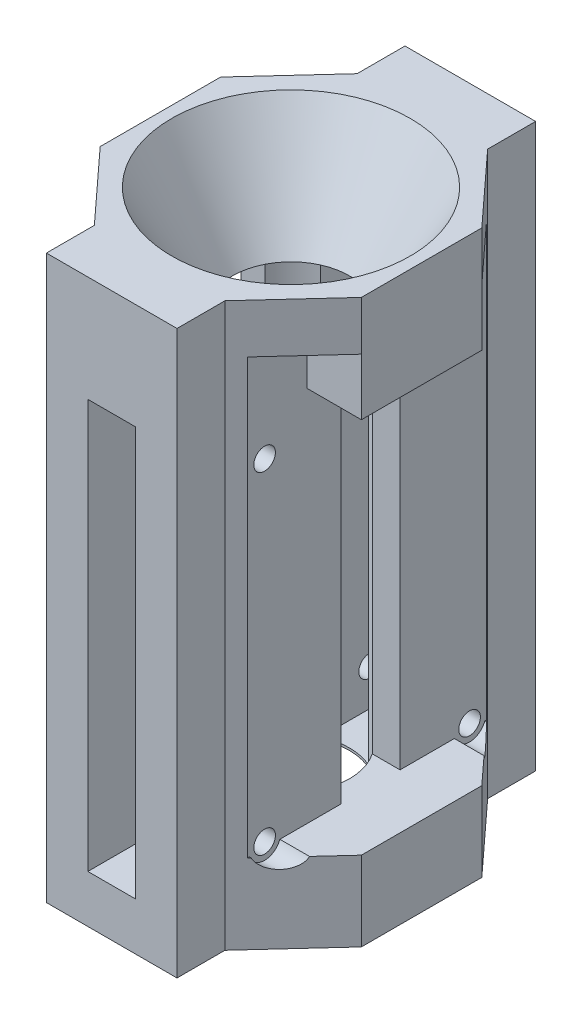
SolidWorks part; units mm, degrees
ref_plane "Alzado" through (0, 0, 0) normal (0, 0, 1) x (1, 0, 0)
ref_plane "Planta" through (0, 0, 0) normal (0, 1, 0) x (1, 0, 0)
ref_plane "Vista lateral" through (0, 0, 0) normal (1, 0, 0) x (0, 0, -1)
sketch "Croquis1" plane through (0, 0, 0) normal (0, 0, 1) x (1, 0, 0)
  line L0 (-110, 93.3) -> (-105, 93.3)
  line L1 (-105, 93.3) -> (-51.5, 0)
  line L2 (-51.5, 0) -> (-51.5, -362)
  line L3 (-51.5, -362) -> (-105, -402)
  line L4 (-105, -402) -> (-110, -402)
  line L5 (-110, -402) -> (-110, 93.3)
  line L6 (0, 0) -> (0, 215.3144) construction
  dimension "D1" = 5
  dimension "D2" = 495.3
  dimension "D3" = 51.5
  dimension "D4" = 362
  dimension "D5" = 110
  dimension "D6" = 40
revolve "Revolución1" add sketch "Croquis1" angle 360 about L6
sketch "Croquis3" plane through (0, 0, 0) normal (1, 0, 0) x (0, 0, -1)
  line L0 (0, 0) -> (0, -402) construction
  line L1 (-110, -402) -> (110, -402) construction
  line L2 (75, 0) -> (75, -362)
  line L3 (-157.87, 0) -> (-75, 0)
  line L4 (-157.87, 0) -> (-157.87, -362)
  line L5 (-157.87, -362) -> (-75, -362)
  line L6 (-75, 0) -> (-75, -362)
  line L7 (157.87, -362) -> (75, -362)
  line L8 (157.87, 0) -> (157.87, -362)
  line L9 (157.87, 0) -> (75, 0)
  dimension "D1" = 362
  dimension "D2" = 47.87
  dimension "D3" = 75
  dimension "D4" = 82.87
  dimension "D5" = 82.87
extrude "Saliente-Extruir1" add sketch "Croquis3" along normal blind 77.5 and the other way blind 77.5
ref_plane "Plano1" through (0, 93.3, 0) normal (0, 1, 0) x (1, 0, 0)
sketch "Croquis4" plane through (0, 93.3, 0) normal (0, 1, 0) x (1, 0, 0)
  line L0 (-77.5, -157.87) -> (77.5, -157.87) construction
  line L1 (-115, 157.87) -> (115, 157.87)
  line L2 (-115, 157.87) -> (-115, -157.87)
  line L3 (-115, -157.87) -> (115, -157.87)
  line L4 (115, 157.87) -> (115, -157.87)
  line L5 (-77.5, 157.87) -> (77.5, 157.87) construction
  circle A0 centre (0, 0) radius 110
  dimension "D1" = 115
  dimension "D2" = 220
  dimension "D3" = 115
extrude "Saliente-Extruir2" add sketch "Croquis4" against normal blind 495.3
ref_plane "Plano6" through (-115, 0, 0) normal (-1, 0, 0) x (0, 0, 1)
ref_plane "Plano7" through (115, 0, 0) normal (1, 0, 0) x (0, 0, -1)
sketch "Croquis5" plane through (0, 0, 0) normal (0, 0, 1) x (1, 0, 0)
  line L1 (-21, 0) -> (21, 0)
  line L2 (-21, 0) -> (-21, -360)
  line L3 (-21, -360) -> (21, -360)
  line L4 (21, 0) -> (21, -360)
  dimension "D1" = 360
  dimension "D2" = 42
extrude "Cortar-Extruir1" cut sketch "Croquis5" against normal through all both and the other way through all
sketch "Croquis6" plane through (0, 0, 0) normal (0, 1, 0) x (1, 0, 0)
  line L0 (-115, 0) -> (115, 0) construction
  line L1 (-115, 157.87) -> (-115, -157.87) construction
  line L2 (115, -157.87) -> (115, 157.87) construction
  line L4 (-30.15, -29) -> (-171.0385, -29)
  line L5 (-30.15, -29) -> (-30.15, 23)
  line L6 (-30.15, 23) -> (-171.0385, 23)
  line L7 (-171.0385, -29) -> (-171.0385, 23)
  line L8 (30.15, -23) -> (191.7754, -23)
  line L9 (30.15, -23) -> (30.15, 29)
  line L10 (30.15, 29) -> (191.7754, 29)
  line L11 (191.7754, -23) -> (191.7754, 29)
  circle A0 centre (0, 0) radius 30.15 construction
  dimension "D1" = 60.3
  dimension "D2" = 30.15
  dimension "D3" = 30.15
  dimension "D4" = 23
  dimension "D5" = 23
  dimension "D6" = 52
  dimension "D7" = 52
  dimension "D8" = 140.8885
  dimension "D9" = 161.6254
extrude "Cortar-Extruir2" cut sketch "Croquis6" against normal blind 332
sketch "Croquis7" plane through (0, 93.3, 0) normal (0, 1, 0) x (1, 0, 0)
  line L0 (-115, 157.87) -> (-57.5, 157.87)
  line L1 (115, 157.87) -> (-115, 157.87) construction
  line L2 (-115, 53.01) -> (-57.5, 115.6371)
  line L3 (-115, 157.87) -> (-115, -157.87) construction
  line L4 (-115, 53.01) -> (-115, 157.87)
  line L5 (-57.5, 115.6371) -> (-57.5, 157.87)
  line L6 (0, 0) -> (0, 157.87) construction
  line L7 (0, 0) -> (115, 0) construction
  line L8 (115, -157.87) -> (115, 157.87) construction
  line L9 (57.5, 115.6371) -> (57.5, 157.87)
  line L10 (115, 53.01) -> (115, 157.87)
  line L11 (115, 53.01) -> (57.5, 115.6371)
  line L12 (115, 157.87) -> (57.5, 157.87)
  line L13 (115, -157.87) -> (57.5, -157.87)
  line L14 (115, -53.01) -> (57.5, -115.6371)
  line L15 (115, -53.01) -> (115, -157.87)
  line L16 (57.5, -115.6371) -> (57.5, -157.87)
  line L17 (-57.5, -115.6371) -> (-57.5, -157.87)
  line L18 (-115, -53.01) -> (-115, -157.87)
  line L19 (-115, -53.01) -> (-57.5, -115.6371)
  line L20 (-115, -157.87) -> (-57.5, -157.87)
  dimension "D1" = 57.5
  dimension "D2" = 104.86
  dimension "D3" = 85.02
extrude "Cortar-Extruir3" cut sketch "Croquis7" against normal up to vertex (495.3 mm away) up to point (115, -402, -157.87)
sketch "Croquis12" plane through (-115, 0, 0) normal (-1, 0, 0) x (0, 0, 1)
  line L0 (-115.6371, -402) -> (-115.6371, 93.3) construction
  line L1 (0, 93.3) -> (0, -402) construction
  line L2 (-53.01, 93.3) -> (53.01, 93.3) construction
  line L3 (-53.01, -402) -> (53.01, -402) construction
  circle A0 centre (-90.2371, -327.07) radius 9.525
  circle A1 centre (-90.2371, -35.052) radius 9.525
  circle A2 centre (90.2371, -35.052) radius 9.525
  circle A3 centre (90.2371, -327.07) radius 9.525
  point P18 (-90.2371, -336.595)
  point P19 (90.2371, -336.595)
  point P20 (90.2371, -25.527)
  point P21 (-90.2371, -25.527)
  dimension "D3" = 19.05
  dimension "D4" = 19.05
  dimension "D1" = 74.93
  dimension "D2" = 35.052
  dimension "D5" = 25.4
extrude "Cortar-Extruir9" cut sketch "Croquis12" against normal up to vertex (230 mm away) up to point (115, -402, -53.01)
sketch "Croquis15" plane through (-115, 0, 0) normal (-1, 0, 0) x (0, 0, 1)
  circle A0 centre (-90.2371, -35.052) radius 14.29
  circle A1 centre (90.2371, -35.052) radius 14.29
  circle A2 centre (90.2371, -327.07) radius 14.29
  circle A3 centre (-90.2371, -327.07) radius 14.29
  point P12 (-90.2371, -20.762)
  point P13 (90.2371, -20.762)
  point P14 (-90.2371, -341.36)
  point P15 (90.2371, -341.36)
  dimension "D1" = 28.58
extrude "Cortar-Extruir10" cut sketch "Croquis15" against normal blind 48
sketch "Croquis16" plane through (115, 0, 0) normal (1, 0, 0) x (0, 0, -1)
  circle A0 centre (-90.2371, -35.052) radius 14.29
  circle A1 centre (90.2371, -35.052) radius 14.29
  circle A2 centre (90.2371, -327.07) radius 14.29
  circle A3 centre (-90.2371, -327.07) radius 14.29
extrude "Cortar-Extruir11" cut sketch "Croquis16" against normal blind 48
sketch "Croquis18" plane through (115, 0, 0) normal (1, 0, 0) x (0, 0, -1)
  line L0 (-115.6371, -402) -> (-115.6371, 93.3) construction
  line L1 (115.6371, 0) -> (-115.6371, 0)
  line L2 (115.6371, 0) -> (115.6371, -332)
  line L3 (115.6371, -332) -> (-115.6371, -332)
  line L4 (-115.6371, 0) -> (-115.6371, -332)
  line L5 (115.6371, -402) -> (115.6371, 93.3) construction
  line L6 (29, -332) -> (29, 0) construction
  line L7 (-23, 0) -> (29, 0) construction
  point P10 (115.6371, -166)
  point P13 (29, -166)
  point P17 (3, 0)
extrude "Cortar-Extruir12" cut sketch "Croquis18" against normal up to surface (48 mm away) up to face at (67, -327.07, 75.9471)
sketch "Croquis19" plane through (-115, 0, 0) normal (-1, 0, 0) x (0, 0, 1)
  line L1 (-115.6371, -332) -> (115.6371, -332)
  line L2 (-115.6371, -332) -> (-115.6371, 0)
  line L3 (-115.6371, 0) -> (115.6371, 0)
  line L4 (115.6371, -332) -> (115.6371, 0)
extrude "Cortar-Extruir13" cut sketch "Croquis19" against normal up to surface (48 mm away) up to face at (-67, -327.07, -75.9471)
sketch "Croquis8" plane through (0, 93.3, 0) normal (0, 1, 0) x (1, 0, 0)
  line L0 (0, -157.87) -> (0, 0)
  line L1 (-57.5, -157.87) -> (57.5, -157.87) construction
  line L2 (0, 0) -> (115, 0)
  line L3 (115, -53.01) -> (115, 53.01) construction
  line L4 (115, 0) -> (115, 201.3043)
  line L5 (115, 201.3043) -> (-183.9384, 201.3043)
  line L6 (-183.9384, 201.3043) -> (-183.9384, -157.87)
  line L7 (-183.9384, -157.87) -> (0, -157.87)
  dimension "D1" = 298.9384
  dimension "D2" = 359.1743
extrude "Cortar-Extruir4" [suppressed] cut sketch "Croquis8" against normal up to vertex
sketch "Croquis9" plane through (0, 93.3, 0) normal (0, 1, 0) x (1, 0, 0)
  line L0 (0, -157.87) -> (0, 0)
  line L1 (-57.5, -157.87) -> (57.5, -157.87) construction
  line L2 (0, 0) -> (-115, 0)
  line L4 (-115, 0) -> (-115, 155.9301)
  line L5 (-115, 155.9301) -> (169.8551, 155.9301)
  line L6 (169.8551, 155.9301) -> (169.8551, -157.87)
  line L7 (169.8551, -157.87) -> (0, -157.87)
  line L8 (-115, 53.01) -> (-115, -53.01) construction
  dimension "D1" = 284.8551
  dimension "D2" = 313.8001
extrude "Cortar-Extruir5" [suppressed] cut sketch "Croquis9" against normal up to vertex
sketch "Croquis10" plane through (0, 93.3, 0) normal (0, 1, 0) x (1, 0, 0)
  line L0 (0, 0) -> (0, 157.87)
  line L1 (57.5, 157.87) -> (-57.5, 157.87) construction
  line L2 (0, 157.87) -> (115, 157.87)
  line L3 (115, 157.87) -> (115, -157.87)
  line L4 (115, -157.87) -> (-115, -157.87)
  line L6 (-115, -157.87) -> (-115, 0)
  line L7 (-115, 0) -> (0, 0)
  line L8 (-115, 53.01) -> (-115, -53.01) construction
  line L9 (115, -53.01) -> (115, 53.01) construction
  line L10 (-57.5, -157.87) -> (57.5, -157.87) construction
extrude "Cortar-Extruir7" [suppressed] cut sketch "Croquis10" against normal up to vertex
sketch "Croquis11" plane through (0, 93.3, 0) normal (0, 1, 0) x (1, 0, 0)
  line L0 (0, 0) -> (115, 0)
  line L1 (115, -53.01) -> (115, 53.01) construction
  line L2 (115, 0) -> (115, -157.87)
  line L3 (0, 0) -> (0, 157.87)
  line L4 (57.5, 157.87) -> (-57.5, 157.87) construction
  line L5 (0, 157.87) -> (-115, 157.87)
  line L6 (-115, 157.87) -> (-115, -157.87)
  line L7 (-115, -157.87) -> (115, -157.87)
  line L8 (-57.5, -157.87) -> (57.5, -157.87) construction
  line L9 (-115, 53.01) -> (-115, -53.01) construction
extrude "Cortar-Extruir8" [suppressed] cut sketch "Croquis11" against normal up to vertex
sketch "Croquis20" plane through (-115, 0, 0) normal (-1, 0, 0) x (0, 0, 1)
  line L1 (-105.29, 0) -> (-53.01, 0)
  line L2 (-105.29, 0) -> (-105.29, 50)
  line L3 (-105.29, 50) -> (-53.01, 50)
  line L4 (105.29, 0) -> (105.29, 50)
  line L5 (53.01, 0) -> (53.01, 50)
  line L6 (53.01, 0) -> (53.01, 93.3) construction
  line L7 (-53.01, 0) -> (-53.01, 50)
  line L8 (-53.01, 0) -> (-53.01, 93.3) construction
  line L9 (53.01, 0) -> (105.29, 0)
  line L10 (53.01, 50) -> (105.29, 50)
  point P15 (0, 0)
  point P16 (-53.01, 50)
  dimension "D1" = 50
extrude "Cortar-Extruir14" cut sketch "Croquis20" against normal up to vertex (48 mm away) up to point (-67, 0, -23)
sketch "Croquis21" plane through (115, 0, 0) normal (1, 0, 0) x (0, 0, -1)
  line L1 (105.29, 50) -> (53.01, 50)
  line L2 (105.29, 50) -> (105.29, 0)
  line L3 (105.29, 0) -> (53.01, 0)
  line L4 (53.01, 50) -> (53.01, 0)
  line L5 (-105.29, 0) -> (-53.01, 0)
  line L6 (-105.29, 0) -> (-105.29, 50)
  line L7 (-105.29, 50) -> (-53.01, 50)
  line L8 (-53.01, 0) -> (-53.01, 50)
extrude "Cortar-Extruir15" cut sketch "Croquis21" against normal up to vertex (48 mm away) up to point (67, 0, 23)
